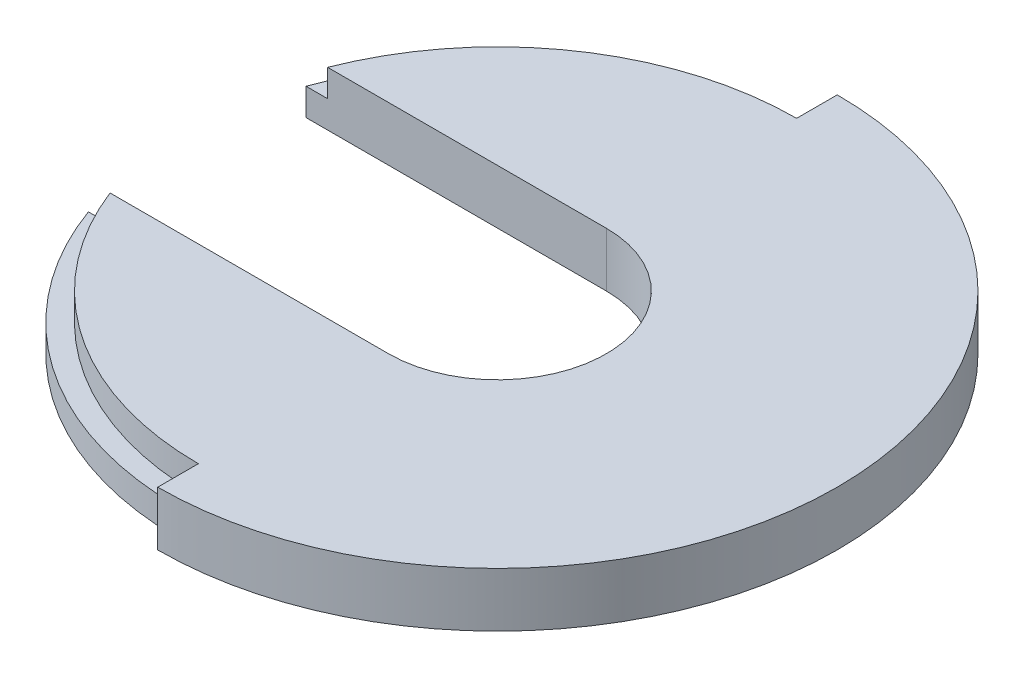
SolidWorks part; units mm, degrees
ref_plane "Front Plane" through (0, 0, 0) normal (0, 0, 1) x (1, 0, 0)
ref_plane "Top Plane" through (0, 0, 0) normal (0, 1, 0) x (1, 0, 0)
ref_plane "Right Plane" through (0, 0, 0) normal (1, 0, 0) x (0, 0, -1)
sketch "Sketch1" plane through (0, 0, 0) normal (0, 1, 0) x (1, 0, 0)
  line L0 (0, 12.5) -> (0, -12.5)
  line L1 (0, 4.0025) -> (-11.8419, 4.0025)
  line L2 (0, -4.0025) -> (-11.8419, -4.0025)
  circle A0 centre (0, 0) radius 12.5
  circle A1 centre (0, 0) radius 11.0045
  circle A2 centre (0, 0) radius 4.0025
  circle A3 centre (0, 0) radius 11.75
  dimension "D1" = 25
  dimension "D2" = 22.009
  dimension "D3" = 8.005
  dimension "D4" = 23.5
extrude "Boss-Extrude1" add sketch "Sketch1" along normal blind 2 contours A3 L0 A0 | L0 A3 A1 region at (0.2627, 0, -11.3773) region at (0.2795, 0, -12.125)
extrude "Boss-Extrude2" add sketch "Sketch1<5>" along normal blind 1 from offset 1 contours L0 A3 A1 | A3 region at (-6.2831, 0, -9.1983)
sketch "Sketch1<5>" plane through (0, 0, 0) normal (0, 1, 0) x (1, 0, 0) same geometry as "Sketch1"
extrude "Cut-Extrude4" cut sketch "Sketch1<8>" along normal blind 11 contours L0 A2 | L0 A2 | A2 L1 A1 L2 | L1 A3 L2 A1 region at (1.6987, 0, 0) region at (-6.9011, 0, 0) region at (-1.6987, 0, 0) region at (-11.1335, 0, 0)
sketch "Sketch1<8>" plane through (0, 0, 0) normal (0, 1, 0) x (1, 0, 0) same geometry as "Sketch1"
extrude "Boss-Extrude3" add sketch "Sketch1<9>" along normal blind 1 contours A2 L0 A1 region at (5.1235, 0, 0)
sketch "Sketch1<9>" plane through (0, 0, 0) normal (0, 1, 0) x (1, 0, 0) same geometry as "Sketch1"
extrude "Boss-Extrude4" add sketch "Sketch1<10>" along normal blind 1 contours L0 A1 L1 | L2 A1 L0 | L2 A3 L0 A1 | L0 A3 L1 A1 region at (-4.083, 0, -6.8972) region at (-4.083, 0, 6.8972) region at (-6.2831, 0, -9.1983) region at (-0.1349, 0, 11.3773)
sketch "Sketch1<10>" plane through (0, 0, 0) normal (0, 1, 0) x (1, 0, 0) same geometry as "Sketch1"
extrude "Cut-Extrude5" cut sketch "Sketch1<11>" against normal blind 1 from surface contours L0 A1 L1 | L0 A3 L1 A1 | L2 A1 L0 | L2 A3 L0 A1 region at (-4.083, 0, -6.8972) region at (-4.083, 0, 6.8972) region at (-6.2831, 0, -9.1983) region at (-0.1349, 0, 11.3773) starting at face at (-1.0047, 2, 0)
sketch "Sketch1<11>" plane through (0, 0, 0) normal (0, 1, 0) x (1, 0, 0) same geometry as "Sketch1"
extrude "Boss-Extrude5" add sketch "Sketch1<12>" along normal blind 2 contours L2 A1 L0 | L0 A1 L1 region at (-4.083, 0, -6.8972) region at (-4.083, 0, 6.8972)
sketch "Sketch1<12>" plane through (0, 0, 0) normal (0, 1, 0) x (1, 0, 0) same geometry as "Sketch1"
